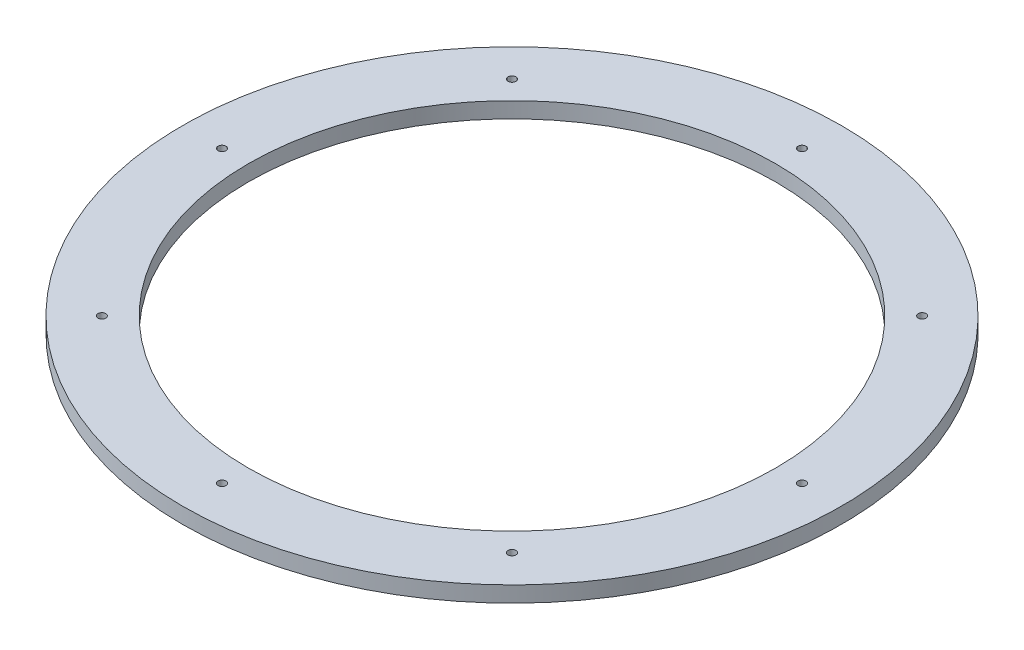
SolidWorks part; units mm, degrees
note: '?' marks a value the reader was unsure of.
ref_plane "Front Plane" through (0, 0, 0) normal (0, 0, 1) x (1, 0, 0)
ref_plane "Top Plane" through (0, 0, 0) normal (0, 1, 0) x (1, 0, 0)
ref_plane "Right Plane" through (0, 0, 0) normal (1, 0, 0) x (0, 0, -1)
sketch "Sketch1" plane through (0, 0, 0) normal (0, 1, 0) x (1, 0, 0)
  line L0 (-100, 0) -> (100, 0) construction
  line L1 (0, 100) -> (0, -100) construction
  line L2 (-70.7107, -70.7107) -> (70.7107, 70.7107) construction
  line L3 (-70.7107, 70.7107) -> (70.7107, -70.7107) construction
  line L4 (70.7107, -70.7107) -> (88.3883, -88.3883) construction
  line L5 (100, 0) -> (125, 0) construction
  line L6 (70.7107, 70.7107) -> (88.3883, 88.3883) construction
  line L7 (0, -100) -> (0, -125) construction
  circle A0 centre (0, 0) radius 100
  circle A1 centre (0, 0) radius 125
  circle A2 centre (0, -110) radius 1.5
  circle A3 centre (77.7817, -77.7817) radius 1.5
  circle A4 centre (110, 0) radius 1.5
  circle A5 centre (77.7817, 77.7817) radius 1.5
  circle A6 centre (0, 110) radius 1.5
  circle A7 centre (-77.7817, 77.7817) radius 1.5
  circle A8 centre (-110, 0) radius 1.5
  circle A9 centre (-77.7817, -77.7817) radius 1.5
  point P11 (0, 0)
  point P14 (0, 0)
  dimension "D1" = 15
  dimension "D2" = 15
  dimension "D3" = 15
  dimension "D4" = 15
extrude "Boss-Extrude1" add sketch "Sketch1" along normal blind 6
convert to sheet metal "Convert-Solid1" [suppressed] bend radius? 10 thickness? 4.75
sketch "Bend-Lines1" [suppressed] plane through (0, 0, 0) normal (0, 1, 0) x (1, 0, 0)
sketch "Bounding-Box1" [suppressed] plane through (0, 0, 0) normal (0, 1, 0) x (1, 0, 0)
sheet metal parameters "Sheet-Metal2" thickness 4.75 parameters "D1"=10
flat pattern "Flat-Pattern2" [suppressed]
sketch "Bend-Lines2" plane through (0, 0, 0) normal (0, 1, 0) x (1, 0, 0)
sketch3d "Bounding-Box2" [suppressed]
  line L0 (-125.0764, 124.9235, 0) -> (-124.9234, -125.0764, 0) construction
  line L1 (124.9235, 125.0764, 0) -> (125.0764, -124.9235, 0) construction
  line L2 (-125.0764, 124.9235, 0) -> (124.9235, 125.0764, 0) construction
  line L3 (-124.9234, -125.0764, 0) -> (125.0764, -124.9235, 0) construction
